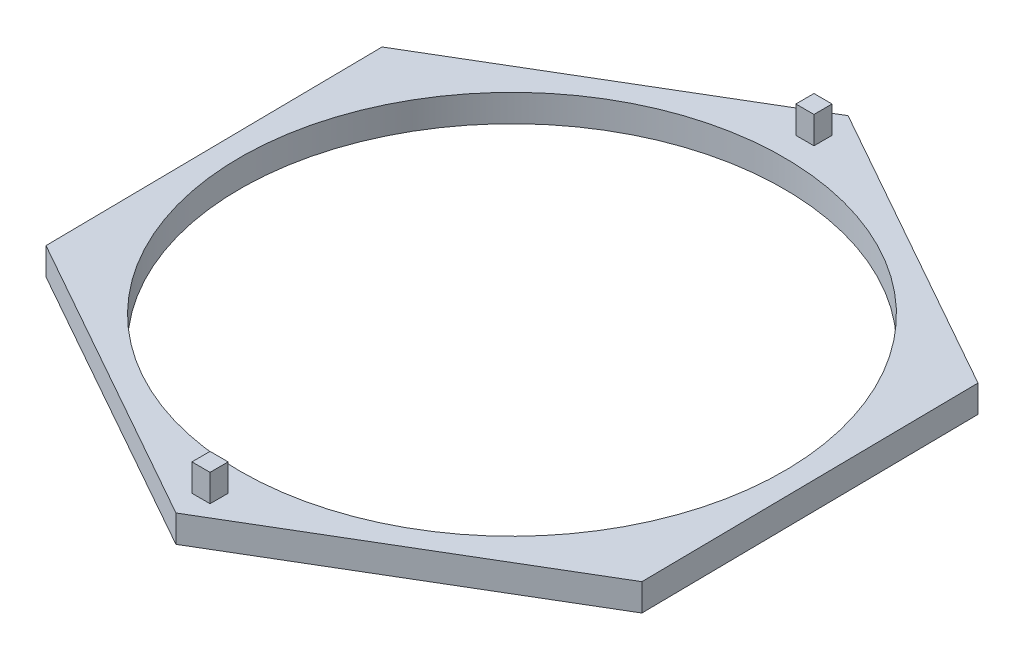
SolidWorks part; units mm, degrees
ref_plane "Front Plane" through (0, 0, 0) normal (0, 0, 1) x (1, 0, 0)
ref_plane "Top Plane" through (0, 0, 0) normal (0, 1, 0) x (1, 0, 0)
ref_plane "Right Plane" through (0, 0, 0) normal (1, 0, 0) x (0, 0, -1)
sketch "Sketch1" plane through (0, 0, 0) normal (0, 1, 0) x (1, 0, 0)
  line L1 (-32.7184, 18.3804) -> (-32.2771, -19.1448)
  line L2 (-32.2771, -19.1448) -> (0.4413, -37.5252)
  line L3 (0.4413, -37.5252) -> (32.7184, -18.3804)
  line L4 (32.7184, -18.3804) -> (32.2771, 19.1448)
  line L5 (32.2771, 19.1448) -> (-0.4413, 37.5252)
  line L6 (-0.4413, 37.5252) -> (-32.7184, 18.3804)
  circle A0 centre (0, 0) radius 32.5 construction
  dimension "D1" = 65
extrude "Boss-Extrude1" add sketch "Sketch1" along normal blind 3
sketch "Sketch2" plane through (0, 3, 0) normal (0, 1, 0) x (1, 0, 0)
  circle A0 centre (0, 0) radius 30
  dimension "D1" = 60
extrude "Cut-Extrude1" cut sketch "Sketch2" against normal through all
sketch "Sketch3" plane through (0, 3, 0) normal (0, 1, 0) x (1, 0, 0)
  line L0 (-0.4413, 37.5252) -> (-0.4413, 29.9968) construction
  line L2 (0.5587, 34.761) -> (-1.4413, 34.761)
  line L3 (0.5587, 34.761) -> (0.5587, 32.761)
  line L4 (0.5587, 32.761) -> (-1.4413, 32.761)
  line L5 (-1.4413, 34.761) -> (-1.4413, 32.761)
  line L6 (0.5587, 34.761) -> (-1.4413, 32.761) construction
  line L7 (0.5587, 32.761) -> (-1.4413, 34.761) construction
  circle A0 centre (0, 0) radius 30 construction
  point P5 (-0.4413, 33.761)
  dimension "D1" = 2
  dimension "D2" = 2
extrude "Boss-Extrude2" add sketch "Sketch3" along normal blind 3
sketch "Sketch4" plane through (0, 3, 0) normal (0, 1, 0) x (1, 0, 0)
  line L0 (0.4413, -37.5252) -> (0.4413, -29.9968) construction
  line L2 (1.4413, -34.761) -> (-0.5587, -34.761)
  line L3 (1.4413, -34.761) -> (1.4413, -32.761)
  line L4 (1.4413, -32.761) -> (-0.5587, -32.761)
  line L5 (-0.5587, -34.761) -> (-0.5587, -32.761)
  line L6 (1.4413, -34.761) -> (-0.5587, -32.761) construction
  line L7 (1.4413, -32.761) -> (-0.5587, -34.761) construction
  circle A0 centre (0, 0) radius 30 construction
  point P5 (0.4413, -33.761)
  dimension "D1" = 2
  dimension "D2" = 2
extrude "Boss-Extrude3" add sketch "Sketch4" along normal blind 3
